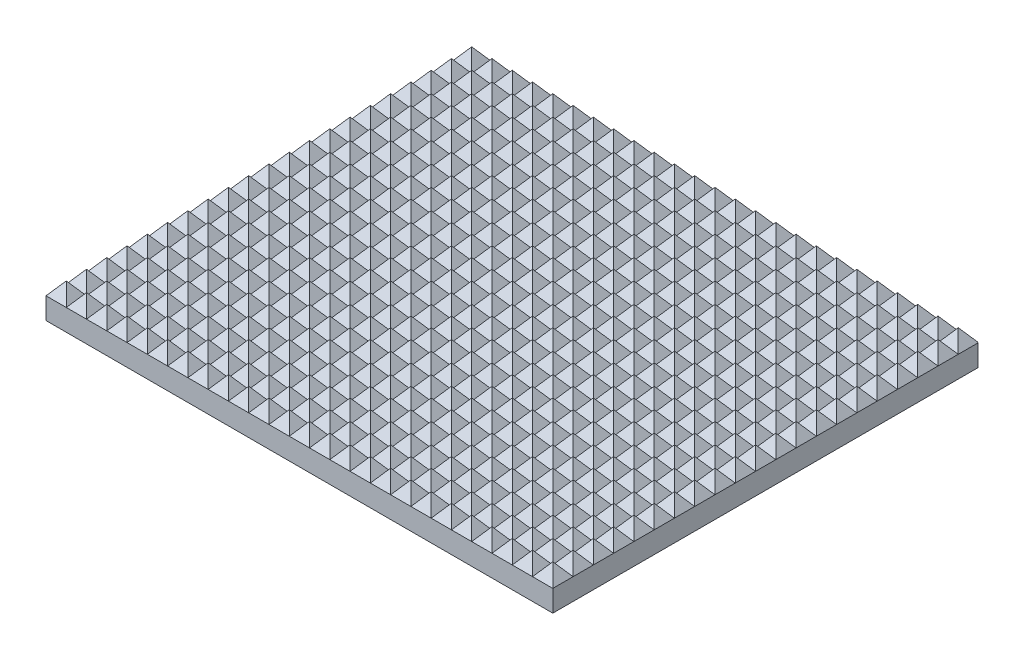
SolidWorks part; units mm, degrees
ref_plane "Front Plane" through (0, 0, 0) normal (0, 0, 1) x (1, 0, 0)
ref_plane "Top Plane" through (0, 0, 0) normal (0, 1, 0) x (1, 0, 0)
ref_plane "Right Plane" through (0, 0, 0) normal (1, 0, 0) x (0, 0, -1)
sketch "Sketch1" plane through (0, 0, 0) normal (0, 1, 0) x (1, 0, 0)
  line L6 (-29.5, 24.75) -> (29.5, 24.75)
  line L28 (-29.5, 24.75) -> (-29.5, -24.75)
  line L29 (-29.5, -24.75) -> (29.5, -24.75)
  line L30 (29.5, 24.75) -> (29.5, -24.75)
  line L31 (-29.5, 24.75) -> (29.5, -24.75) construction
  line L32 (-29.5, -24.75) -> (29.5, 24.75) construction
  circle A1 centre (0, 0) radius 3
  point P0 (0, 0)
  dimension "D3" = 6
  dimension "D1" = 59
  dimension "D2" = 49.5
extrude "Boss-Extrude1" add sketch "Sketch1" along normal blind 1.5
sketch "Sketch2" plane through (0, 0, -24.75) normal (0, 0, -1) x (-1, 0, 0)
  line L0 (-29.5, 1.5) -> (-29.5, 0) construction
  line L1 (-29.5, 1.5) -> (29.5, 1.5)
  line L2 (-29.5, 1.5) -> (-29.5, 2.5)
  line L4 (29.5, 1.5) -> (29.5, 2.5)
  line L5 (-1.18, 2.5) -> (0, 4)
  line L6 (0, 55) -> (0, -55) construction
  line L7 (1.18, 2.5) -> (0, 4)
  line L8 (1.18, 2.5) -> (2.36, 4)
  line L9 (3.54, 2.5) -> (2.36, 4)
  line L10 (3.54, 2.5) -> (4.72, 4)
  line L11 (5.9, 2.5) -> (4.72, 4)
  line L12 (5.9, 2.5) -> (7.08, 4)
  line L13 (8.26, 2.5) -> (7.08, 4)
  line L14 (8.26, 2.5) -> (9.44, 4)
  line L15 (10.62, 2.5) -> (9.44, 4)
  line L16 (10.62, 2.5) -> (11.8, 4)
  line L17 (12.98, 2.5) -> (11.8, 4)
  line L18 (12.98, 2.5) -> (14.16, 4)
  line L19 (15.34, 2.5) -> (14.16, 4)
  line L20 (15.34, 2.5) -> (16.52, 4)
  line L21 (17.7, 2.5) -> (16.52, 4)
  line L22 (17.7, 2.5) -> (18.88, 4)
  line L23 (20.06, 2.5) -> (18.88, 4)
  line L24 (20.06, 2.5) -> (21.24, 4)
  line L25 (22.42, 2.5) -> (21.24, 4)
  line L26 (22.42, 2.5) -> (23.6, 4)
  line L27 (24.78, 2.5) -> (23.6, 4)
  line L28 (24.78, 2.5) -> (25.96, 4)
  line L29 (27.14, 2.5) -> (25.96, 4)
  line L30 (27.14, 2.5) -> (28.32, 4)
  line L31 (29.5, 2.5) -> (28.32, 4)
  line L32 (-29.5, 2.5) -> (-28.32, 4)
  line L33 (-27.14, 2.5) -> (-28.32, 4)
  line L34 (-27.14, 2.5) -> (-25.96, 4)
  line L35 (-24.78, 2.5) -> (-25.96, 4)
  line L36 (-24.78, 2.5) -> (-23.6, 4)
  line L37 (-22.42, 2.5) -> (-23.6, 4)
  line L38 (-22.42, 2.5) -> (-21.24, 4)
  line L39 (-20.06, 2.5) -> (-21.24, 4)
  line L40 (-20.06, 2.5) -> (-18.88, 4)
  line L41 (-17.7, 2.5) -> (-18.88, 4)
  line L42 (-17.7, 2.5) -> (-16.52, 4)
  line L43 (-15.34, 2.5) -> (-16.52, 4)
  line L44 (-15.34, 2.5) -> (-14.16, 4)
  line L45 (-12.98, 2.5) -> (-14.16, 4)
  line L46 (-12.98, 2.5) -> (-11.8, 4)
  line L47 (-10.62, 2.5) -> (-11.8, 4)
  line L48 (-10.62, 2.5) -> (-9.44, 4)
  line L49 (-8.26, 2.5) -> (-9.44, 4)
  line L50 (-8.26, 2.5) -> (-7.08, 4)
  line L51 (-5.9, 2.5) -> (-7.08, 4)
  line L52 (-5.9, 2.5) -> (-4.72, 4)
  line L53 (-3.54, 2.5) -> (-4.72, 4)
  line L54 (-3.54, 2.5) -> (-2.36, 4)
  line L55 (-1.18, 2.5) -> (-2.36, 4)
  dimension "D1" = 1
  dimension "D2" = 1.5
  dimension "D3" = 13
extrude "Boss-Extrude2" add sketch "Sketch2" against normal up to surface (49.5 mm away) up to face at (0, 0.75, 24.75)
sketch "Sketch3" plane through (0, 0, 0) normal (0, -1, 0) x (-1, 0, 0)
  line L0 (0, 55) -> (0, -55) construction
  line L2 (-1.75, -2.4367) -> (-1.75, -5)
  line L3 (-1.75, -5) -> (1.75, -5)
  line L4 (1.75, -2.4367) -> (1.75, -5)
  arc A0 (1.75, -2.4367) -> (-1.75, -2.4367) centre (0, 0) ccw
  dimension "D2" = 6
  dimension "D1" = 3.5
  dimension "D3" = 5
  dimension "D4" = 1.75
extrude "Cut-Extrude1" cut sketch "Sketch3" against normal blind 1
sketch "Sketch4" plane through (29.5, 0, 0) normal (1, 0, 0) x (0, 0, -1)
  line L1 (-24.75, 4) -> (-24.75, 2.5) construction
  line L2 (-24.75, 4) -> (24.75, 4) construction
  line L3 (-24, 4) -> (-24.75, 4)
  line L4 (-24.75, 4) -> (-24.75, 3.25)
  arc A0 (-24.75, 3.25) -> (-24, 4) centre (-24, 3.25) cw
extrude "Cut-Extrude3" [suppressed] cut sketch "Sketch4" against normal through all
mirror "Mirror1" [suppressed] about plane through (0, 0, 0) normal (0, 0, 1)
sketch "Sketch5" plane through (0, 1.5, 0) normal (0, -1, 0) x (1, 0, 0)
  circle A0 centre (0, 0) radius 3
  dimension "D1" = 6
extrude "Boss-Extrude3" add sketch "Sketch5" along normal blind 0.5
sketch "Sketch6" plane through (0, 1, 0) normal (0, -1, 0) x (1, 0, 0)
  line L1 (1.75, 5) -> (-1.75, 5)
  line L2 (1.75, 5) -> (1.75, 2.4367)
  line L3 (1.75, 2.4367) -> (-1.75, 2.4367)
  line L4 (-1.75, 5) -> (-1.75, 2.4367)
extrude "Cut-Extrude4" cut sketch "Sketch6" against normal blind 0.5
chamfer "Chamfer3" distance 1.5 angle 45 1 edges at (0, 0, 5)
sketch "Sketch7" plane through (0, 0, 24.75) normal (0, 0, 1) x (1, 0, 0)
  line L1 (-29.5, 2.5) -> (29.5, 2.5)
  line L2 (-29.5, 2.5) -> (-29.5, 4.5865)
  line L3 (-29.5, 4.5865) -> (29.5, 4.5865)
  line L4 (29.5, 2.5) -> (29.5, 4.5865)
extrude "Cut-Extrude5" [suppressed] cut sketch "Sketch7" against normal through all
sketch "Sketch9" plane through (29.5, 0, 0) normal (1, 0, 0) x (0, 0, -1)
  line L53 (-24.75, 2.5) -> (-23.57, 4)
  line L54 (-24.75, 4) -> (24.75, 4) construction
  line L55 (-23.57, 4) -> (-22.39, 2.5)
  line L56 (-24.75, 2.5) -> (24.75, 2.5) construction
  line L57 (-22.39, 2.5) -> (-21.21, 4)
  line L58 (-21.21, 4) -> (-20.03, 2.5)
  line L59 (-20.03, 2.5) -> (-18.85, 4)
  line L60 (-18.85, 4) -> (-17.67, 2.5)
  line L61 (-17.67, 2.5) -> (-16.49, 4)
  line L62 (-16.49, 4) -> (-15.31, 2.5)
  line L63 (-15.31, 2.5) -> (-14.13, 4)
  line L64 (-14.13, 4) -> (-12.95, 2.5)
  line L65 (-12.95, 2.5) -> (-11.77, 4)
  line L66 (-11.77, 4) -> (-10.59, 2.5)
  line L67 (-10.59, 2.5) -> (-9.41, 4)
  line L68 (-9.41, 4) -> (-8.23, 2.5)
  line L69 (-8.23, 2.5) -> (-7.05, 4)
  line L70 (-7.05, 4) -> (-5.87, 2.5)
  line L71 (-5.87, 2.5) -> (-4.69, 4)
  line L72 (-4.69, 4) -> (-3.51, 2.5)
  line L73 (-3.51, 2.5) -> (-2.33, 4)
  line L74 (-2.33, 4) -> (-1.15, 2.5)
  line L75 (-1.15, 2.5) -> (0.03, 4)
  line L76 (0.03, 4) -> (1.21, 2.5)
  line L77 (1.21, 2.5) -> (2.39, 4)
  line L78 (2.39, 4) -> (3.57, 2.5)
  line L79 (3.57, 2.5) -> (4.75, 4)
  line L80 (4.75, 4) -> (5.93, 2.5)
  line L81 (5.93, 2.5) -> (7.11, 4)
  line L82 (7.11, 4) -> (8.29, 2.5)
  line L83 (8.29, 2.5) -> (9.47, 4)
  line L84 (9.47, 4) -> (10.65, 2.5)
  line L85 (10.65, 2.5) -> (11.83, 4)
  line L86 (11.83, 4) -> (13.01, 2.5)
  line L87 (13.01, 2.5) -> (14.19, 4)
  line L88 (14.19, 4) -> (15.37, 2.5)
  line L89 (15.37, 2.5) -> (16.55, 4)
  line L90 (16.55, 4) -> (17.73, 2.5)
  line L91 (17.73, 2.5) -> (18.91, 4)
  line L92 (18.91, 4) -> (20.09, 2.5)
  line L93 (20.09, 2.5) -> (21.27, 4)
  line L94 (21.27, 4) -> (22.45, 2.5)
  line L95 (22.45, 2.5) -> (23.63, 4)
  line L96 (23.63, 4) -> (24.81, 2.5)
  line L97 (-24.75, 2.5) -> (-24.75, 6.4088)
  line L98 (-24.75, 6.4088) -> (24.81, 6.4088)
  line L99 (24.81, 6.4088) -> (24.81, 2.5)
  dimension "D3" = 2.36
  dimension "D4" = 1.18
  dimension "D5" = 21
extrude "Cut-Extrude6" cut sketch "Sketch9" against normal through all
